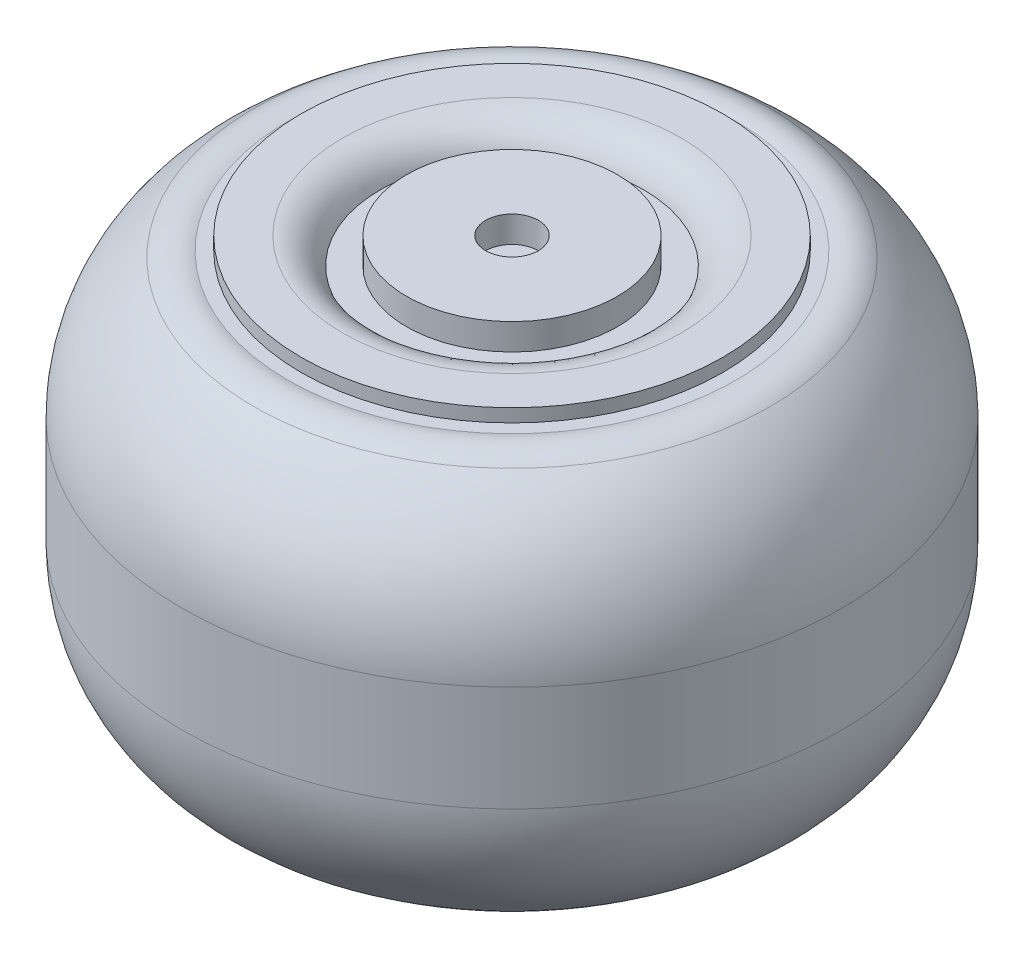
SolidWorks part; units mm, degrees
ref_plane "前视基准面" through (0, 0, 0) normal (0, 0, 1) x (1, 0, 0)
ref_plane "上视基准面" through (0, 0, 0) normal (0, 1, 0) x (1, 0, 0)
ref_plane "右视基准面" through (0, 0, 0) normal (1, 0, 0) x (0, 0, -1)
sketch "草图1" plane through (0, 0, 0) normal (1, 0, 0) x (0, 0, -1)
  line L0 (17, 32) -> (23, 32)
  line L1 (0, 0) -> (37.5, 0) construction
  line L2 (0, 0) -> (0, 32)
  line L3 (0, 32) -> (8, 32)
  line L4 (25, 2) -> (25, 30)
  line L5 (9, 32) -> (15, 32)
  line L6 (0, 16) -> (25, 16) construction
  line L7 (25, 30) -> (23, 30)
  line L8 (23, 32) -> (23, 30)
  line L9 (8, 32) -> (8, 31)
  line L10 (15, 32) -> (15, 30)
  line L11 (15, 30) -> (17, 30)
  line L12 (17, 32) -> (17, 30)
  line L13 (8, 31) -> (9, 31)
  line L14 (9, 32) -> (9, 31)
  line L15 (9, 0) -> (9, 1)
  line L16 (8, 1) -> (9, 1)
  line L17 (17, 0) -> (17, 2)
  line L18 (15, 2) -> (17, 2)
  line L19 (15, 0) -> (15, 2)
  line L20 (8, 0) -> (8, 1)
  line L21 (23, 0) -> (23, 2)
  line L22 (25, 2) -> (23, 2)
  line L23 (9, 0) -> (15, 0)
  line L24 (0, 0) -> (8, 0)
  line L25 (17, 0) -> (23, 0)
  point P12 (23, 31)
  dimension "D1" = 25
  dimension "D2" = 32
  dimension "D3" = 2
  dimension "D4" = 2
  dimension "D5" = 2
  dimension "D6" = 6
  dimension "D7" = 2
  dimension "D8" = 1
  dimension "D9" = 8
  dimension "D10" = 1
revolve "旋转1" add sketch "草图1" angle 360 about L4
fillet "圆角1" radius 13 2 edges at (0, 32, -50) (0, 0, -50)
fillet "圆角3" radius 3 1 edges at (0, 32, -35)
fillet "圆角4" radius 3 1 edges at (0, 32, -42)
